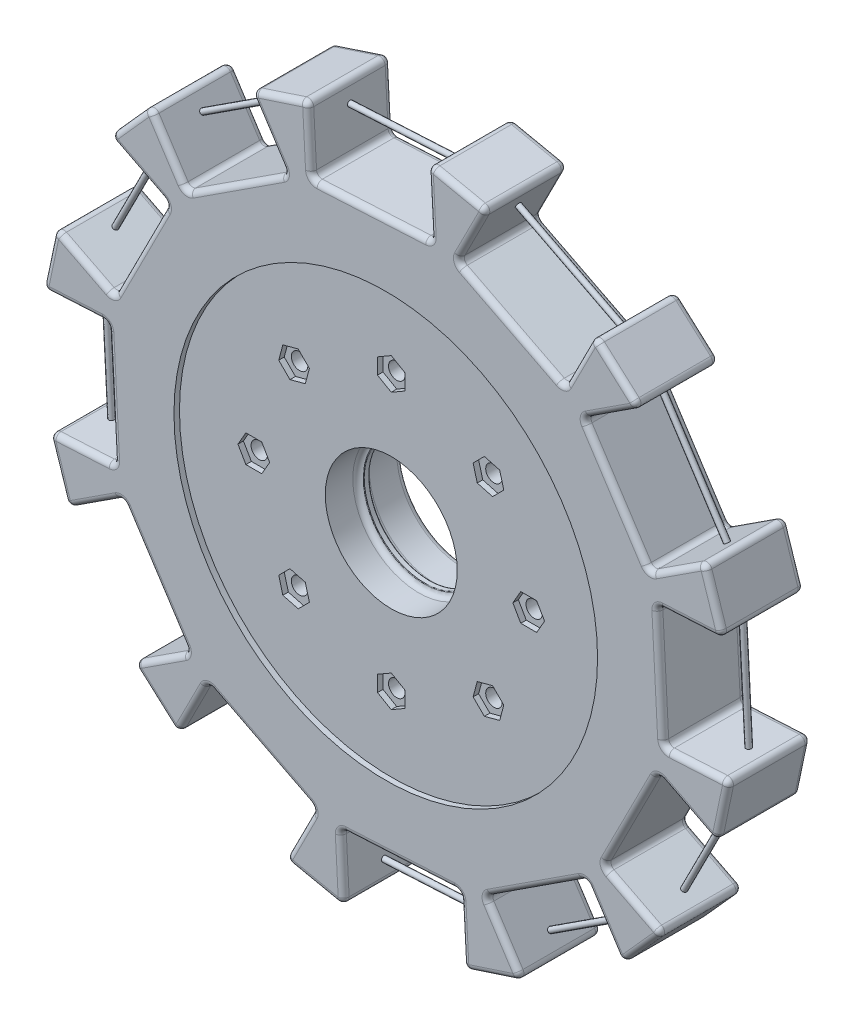
SolidWorks part; units mm, degrees
ref_plane "Front Plane" through (0, 0, 0) normal (0, 0, 1) x (1, 0, 0)
ref_plane "Top Plane" through (0, 0, 0) normal (0, 1, 0) x (1, 0, 0)
ref_plane "Right Plane" through (0, 0, 0) normal (1, 0, 0) x (0, 0, -1)
sketch "Sketch1" plane through (0, 0, 0) normal (0, 0, 1) x (1, 0, 0)
  line L0 (-18.6746, 48.6931) -> (-23.9631, 56.823)
  line L1 (40.0812, -31.4875) -> (49.0527, -13.8463)
  line L2 (50.455, -7.2284) -> (49.4041, 12.5351)
  line L3 (47.3095, 18.9676) -> (36.5176, 35.5577)
  line L4 (31.4875, 40.0812) -> (13.8463, 49.0527)
  line L5 (7.2284, 50.455) -> (-12.5351, 49.4041)
  line L6 (-18.9676, 47.3095) -> (-35.5577, 36.5176)
  line L7 (-40.0812, 31.4875) -> (-49.0527, 13.8463)
  line L8 (-50.455, 7.2284) -> (-49.4041, -12.5351)
  line L9 (-47.3095, -18.9676) -> (-36.5176, -35.5577)
  line L10 (-31.4875, -40.0812) -> (-13.8463, -49.0527)
  line L11 (-7.2284, -50.455) -> (12.5351, -49.4041)
  line L12 (18.9676, -47.3095) -> (35.5577, -36.5176)
  line L13 (-13.5868, 50.3495) -> (-14.1025, 60.0477)
  line L14 (-23.4359, 58.3186) -> (-15.4122, 60.945)
  line L15 (8.1738, 51.5067) -> (7.6588, 61.1917)
  line L16 (8.8632, 62.2234) -> (17.1251, 60.486)
  line L17 (13.4083, 50.3974) -> (17.8107, 59.0541)
  line L18 (32.8321, 40.5192) -> (37.2286, 49.1642)
  line L19 (38.7875, 49.4554) -> (45.0738, 43.8198)
  line L20 (36.8106, 36.9413) -> (44.9516, 42.237)
  line L21 (48.6931, 18.6746) -> (56.823, 23.9631)
  line L22 (58.3186, 23.4359) -> (60.945, 15.4122)
  line L23 (50.3495, 13.5868) -> (60.0477, 14.1025)
  line L24 (51.5067, -8.1738) -> (61.1917, -7.6588)
  line L25 (62.2234, -8.8632) -> (60.486, -17.1251)
  line L26 (50.3974, -13.4083) -> (59.0541, -17.8107)
  line L27 (40.5192, -32.8321) -> (49.1642, -37.2286)
  line L28 (49.4554, -38.7875) -> (43.8198, -45.0738)
  line L29 (36.9413, -36.8106) -> (42.237, -44.9516)
  line L30 (18.6746, -48.6931) -> (23.9631, -56.823)
  line L31 (23.4359, -58.3186) -> (15.4122, -60.945)
  line L32 (13.5868, -50.3495) -> (14.1025, -60.0477)
  line L33 (-8.1738, -51.5067) -> (-7.6588, -61.1917)
  line L34 (-8.8632, -62.2234) -> (-17.1251, -60.486)
  line L35 (-13.4083, -50.3974) -> (-17.8107, -59.0541)
  line L36 (-32.8321, -40.5192) -> (-37.2286, -49.1642)
  line L37 (-38.7875, -49.4554) -> (-45.0738, -43.8198)
  line L38 (-36.8106, -36.9413) -> (-44.9516, -42.237)
  line L39 (-48.6931, -18.6746) -> (-56.823, -23.9631)
  line L40 (-58.3186, -23.4359) -> (-60.945, -15.4122)
  line L41 (-50.3495, -13.5868) -> (-60.0477, -14.1025)
  line L42 (-51.5067, 8.1738) -> (-61.1917, 7.6588)
  line L43 (-62.2234, 8.8632) -> (-60.486, 17.1251)
  line L44 (-50.3974, 13.4083) -> (-59.0541, 17.8107)
  line L45 (-40.5192, 32.8321) -> (-49.1642, 37.2286)
  line L46 (-49.4554, 38.7875) -> (-43.8198, 45.0738)
  line L47 (-36.9413, 36.8106) -> (-42.237, 44.9516)
  circle A0 centre (0, 0) radius 50 construction
  arc A1 (-49.0527, 13.8463) -> (-50.3974, 13.4083) centre (-49.9441, 14.2996) cw
  arc A2 (-50.455, 7.2284) -> (-51.5067, 8.1738) centre (-51.4536, 7.1753) ccw
  arc A3 (-47.3095, -18.9676) -> (-48.6931, -18.6746) centre (-48.1478, -19.5129) ccw
  arc A4 (-49.4041, -12.5351) -> (-50.3495, -13.5868) centre (-50.4026, -12.5882) cw
  arc A5 (-36.5176, -35.5577) -> (-36.8106, -36.9413) centre (-37.3559, -36.103) cw
  arc A6 (-31.4875, -40.0812) -> (-32.8321, -40.5192) centre (-31.9408, -40.9725) ccw
  arc A7 (-13.8463, -49.0527) -> (-13.4083, -50.3974) centre (-14.2996, -49.9441) cw
  arc A8 (-7.2284, -50.455) -> (-8.1738, -51.5067) centre (-7.1753, -51.4536) ccw
  arc A9 (13.5868, -50.3495) -> (12.5351, -49.4041) centre (12.5882, -50.4026) ccw
  arc A10 (18.9676, -47.3095) -> (18.6746, -48.6931) centre (19.5129, -48.1478) ccw
  arc A11 (35.5577, -36.5176) -> (36.9413, -36.8106) centre (36.103, -37.3559) cw
  arc A12 (40.5192, -32.8321) -> (40.0812, -31.4875) centre (40.9725, -31.9408) cw
  arc A13 (49.0527, -13.8463) -> (50.3974, -13.4083) centre (49.9441, -14.2996) cw
  arc A14 (50.455, -7.2284) -> (51.5067, -8.1738) centre (51.4536, -7.1753) ccw
  arc A15 (49.4041, 12.5351) -> (50.3495, 13.5868) centre (50.4026, 12.5882) cw
  arc A16 (47.3095, 18.9676) -> (48.6931, 18.6746) centre (48.1478, 19.5129) ccw
  arc A17 (31.4875, 40.0812) -> (32.8321, 40.5192) centre (31.9408, 40.9725) ccw
  arc A18 (36.5176, 35.5577) -> (36.8106, 36.9413) centre (37.3559, 36.103) cw
  arc A19 (7.2284, 50.455) -> (8.1738, 51.5067) centre (7.1753, 51.4536) ccw
  arc A20 (13.8463, 49.0527) -> (13.4083, 50.3974) centre (14.2996, 49.9441) cw
  arc A21 (-12.5351, 49.4041) -> (-13.5868, 50.3495) centre (-12.5882, 50.4026) cw
  arc A22 (-18.9676, 47.3095) -> (-18.6746, 48.6931) centre (-19.5129, 48.1478) ccw
  arc A23 (-35.5577, 36.5176) -> (-36.9413, 36.8106) centre (-36.103, 37.3559) cw
  arc A24 (-40.0812, 31.4875) -> (-40.5192, 32.8321) centre (-40.9725, 31.9408) ccw
  arc A25 (-60.486, 17.1251) -> (-59.0541, 17.8107) centre (-59.5074, 16.9193) cw
  arc A26 (-61.1917, 7.6588) -> (-62.2234, 8.8632) centre (-61.2448, 8.6574) cw
  arc A27 (-60.945, -15.4122) -> (-60.0477, -14.1025) centre (-59.9946, -15.1011) cw
  arc A28 (-56.823, -23.9631) -> (-58.3186, -23.4359) centre (-57.3683, -23.1249) cw
  arc A29 (-45.0738, -43.8198) -> (-44.9516, -42.237) centre (-44.4063, -43.0752) cw
  arc A30 (-37.2286, -49.1642) -> (-38.7875, -49.4554) centre (-38.1199, -48.7109) cw
  arc A31 (-17.1251, -60.486) -> (-17.8107, -59.0541) centre (-16.9193, -59.5074) cw
  arc A32 (-7.6588, -61.1917) -> (-8.8632, -62.2234) centre (-8.6574, -61.2448) cw
  arc A33 (15.4122, -60.945) -> (14.1025, -60.0477) centre (15.1011, -59.9946) cw
  arc A34 (23.9631, -56.823) -> (23.4359, -58.3186) centre (23.1249, -57.3683) cw
  arc A35 (43.8198, -45.0738) -> (42.237, -44.9516) centre (43.0752, -44.4063) cw
  arc A36 (49.4554, -38.7875) -> (49.1642, -37.2286) centre (48.7109, -38.1199) ccw
  arc A37 (60.486, -17.1251) -> (59.0541, -17.8107) centre (59.5074, -16.9193) cw
  arc A38 (61.1917, -7.6588) -> (62.2234, -8.8632) centre (61.2448, -8.6574) cw
  arc A39 (56.823, 23.9631) -> (58.3186, 23.4359) centre (57.3683, 23.1249) cw
  arc A40 (60.945, 15.4122) -> (60.0477, 14.1025) centre (59.9946, 15.1011) cw
  arc A41 (37.2286, 49.1642) -> (38.7875, 49.4554) centre (38.1199, 48.7109) cw
  arc A42 (45.0738, 43.8198) -> (44.9516, 42.237) centre (44.4063, 43.0752) cw
  arc A43 (17.1251, 60.486) -> (17.8107, 59.0541) centre (16.9193, 59.5074) cw
  arc A44 (7.6588, 61.1917) -> (8.8632, 62.2234) centre (8.6574, 61.2448) cw
  arc A45 (-14.1025, 60.0477) -> (-15.4122, 60.945) centre (-15.1011, 59.9946) ccw
  arc A46 (-23.4359, 58.3186) -> (-23.9631, 56.823) centre (-23.1249, 57.3683) ccw
  arc A47 (-49.1642, 37.2286) -> (-49.4554, 38.7875) centre (-48.7109, 38.1199) cw
  arc A48 (-43.8198, 45.0738) -> (-42.237, 44.9516) centre (-43.0752, 44.4063) cw
  point P66 (0, 0)
  dimension "D1" = 100
  dimension "D7" = 1
  dimension "D2" = 1
  dimension "D6" = 12
extrude "Boss-Extrude1" add sketch "Sketch1" along normal blind 15
sketch "Sketch3" plane through (0, 0, 15) normal (0, 0, 1) x (1, 0, 0)
  circle A0 centre (0, 0) radius 12
  dimension "D1" = 24
extrude "Cut-Extrude1" cut sketch "Sketch3" against normal blind 7
sketch "Sketch4" plane through (0, 0, 0) normal (0, 0, -1) x (-1, 0, 0)
  circle A0 centre (0, 0) radius 12
  dimension "D1" = 24
extrude "Cut-Extrude2" cut sketch "Sketch4" against normal blind 7
sketch "Sketch5" plane through (0, 0, 7) normal (0, 0, -1) x (-1, 0, 0)
  circle A0 centre (0, 0) radius 11
  dimension "D1" = 22
extrude "Cut-Extrude3" cut sketch "Sketch5" against normal blind 7
fillet "Fillet1" radius 1 194 edges at (-27.2627, 41.9136, 15) (-18.5345, 47.9406, 15) (-21.3189, 52.758, 15) (-24.068, 57.7007, 15) (-19.4241, 59.6318, 15) (-14.5359, 60.8195, 15) (-13.8447, 55.1986, 15) (-13.2568, 49.659, 15) (-2.6534, 49.9295, 15) (7.9189, 50.7851, 15) (7.9163, 56.3492, 15) (8.0068, 62.0043, 15) (12.9942, 61.3547, 15) (17.8213, 59.9392, 15) (15.6095, 54.7257, 15) (13.3488, 49.6343, 15) (22.6669, 44.5669, 15) (32.2505, 40.0217, 15) (35.0304, 44.8417, 15) (37.9363, 49.6938, 15) (41.9306, 46.6376, 15) (45.4033, 42.9982, 15) (40.8811, 39.5891, 15) (36.3776, 36.3102, 15) (41.9136, 27.2627, 15) (47.9406, 18.5345, 15) (52.758, 21.3189, 15) (57.7007, 24.068, 15) (59.6318, 19.4241, 15) (60.8195, 14.5359, 15) (55.1986, 13.8447, 15) (49.659, 13.2568, 15) (49.9295, 2.6534, 15) (50.7851, -7.9189, 15) (56.3492, -7.9163, 15) (62.0043, -8.0068, 15) (61.3547, -12.9942, 15) (59.9392, -17.8213, 15) (54.7257, -15.6095, 15) (49.6343, -13.3488, 15) (44.5669, -22.6669, 15) (40.0217, -32.2505, 15) (44.8417, -35.0304, 15) (49.6938, -37.9363, 15) (46.6376, -41.9306, 15) (42.9982, -45.4033, 15) (39.5891, -40.8811, 15) (36.3102, -36.3776, 15) (27.2627, -41.9136, 15) (18.5345, -47.9406, 15) (21.3189, -52.758, 15) (24.068, -57.7007, 15) (19.4241, -59.6318, 15) (14.5359, -60.8195, 15) (13.8447, -55.1986, 15) (13.2568, -49.659, 15) (2.6534, -49.9295, 15) (-7.9189, -50.7851, 15) (-7.9163, -56.3492, 15) (-8.0068, -62.0043, 15) (-12.9942, -61.3547, 15) (-17.8213, -59.9392, 15) (-15.6095, -54.7257, 15) (-13.3488, -49.6343, 15) (-22.6669, -44.5669, 15) (-32.2505, -40.0217, 15) (-35.0304, -44.8417, 15) (-37.9363, -49.6938, 15) (-41.9306, -46.6376, 15) (-45.4033, -42.9982, 15) (-40.8811, -39.5891, 15) (-36.3776, -36.3102, 15) (-41.9136, -27.2627, 15) (-47.9406, -18.5345, 15) (-52.758, -21.3189, 15) (-57.7007, -24.068, 15) (-59.6318, -19.4241, 15) (-60.8195, -14.5359, 15) (-55.1986, -13.8447, 15) (-49.659, -13.2568, 15) (-49.9295, -2.6534, 15) (-50.7851, 7.9189, 15) (-56.3492, 7.9163, 15) (-62.0043, 8.0068, 15) (-61.3547, 12.9942, 15) (-59.9392, 17.8213, 15) (-54.7257, 15.6095, 15) (-49.6343, 13.3488, 15) (-44.5669, 22.6669, 15) (-40.0217, 32.2505, 15) (-44.8417, 35.0304, 15) (-49.6938, 37.9363, 15) (-46.6376, 41.9306, 15) (-42.9982, 45.4033, 15) (-39.5891, 40.8811, 15) (-36.3102, 36.3776, 15) (12, 0, 15) (-39.5891, 40.8811, 0) (-42.9982, 45.4033, 0) (-46.6376, 41.9306, 0) (-49.6938, 37.9363, 0) (-44.8417, 35.0304, 0) (-40.0217, 32.2505, 0) (-44.5669, 22.6669, 0) (-49.6343, 13.3488, 0) (-54.7257, 15.6095, 0) (-59.9392, 17.8213, 0) (-61.3547, 12.9942, 0) (-62.0043, 8.0068, 0) (-56.3492, 7.9163, 0) (-50.7851, 7.9189, 0) (-49.9295, -2.6534, 0) (-49.659, -13.2568, 0) (-55.1986, -13.8447, 0) (-60.8195, -14.5359, 0) (-59.6318, -19.4241, 0) (-57.7007, -24.068, 0) (-52.758, -21.3189, 0) (-47.9406, -18.5345, 0) (-41.9136, -27.2627, 0) (-36.3776, -36.3102, 0) (-40.8811, -39.5891, 0) (-45.4033, -42.9982, 0) (-41.9306, -46.6376, 0) (-37.9363, -49.6938, 0) (-35.0304, -44.8417, 0) (-32.2505, -40.0217, 0) (-22.6669, -44.5669, 0) (-13.3488, -49.6343, 0) (-15.6095, -54.7257, 0) (-17.8213, -59.9392, 0) (-12.9942, -61.3547, 0) (-8.0068, -62.0043, 0) (-7.9163, -56.3492, 0) (-7.9189, -50.7851, 0) (2.6534, -49.9295, 0) (13.2568, -49.659, 0) (13.8447, -55.1986, 0) (14.5359, -60.8195, 0) (19.4241, -59.6318, 0) (24.068, -57.7007, 0) (21.3189, -52.758, 0) (18.5345, -47.9406, 0) (27.2627, -41.9136, 0) (36.3102, -36.3776, 0) (39.5891, -40.8811, 0) (42.9982, -45.4033, 0) (46.6376, -41.9306, 0) (49.6938, -37.9363, 0) (44.8417, -35.0304, 0) (40.0217, -32.2505, 0) (44.5669, -22.6669, 0) (49.6343, -13.3488, 0) (54.7257, -15.6095, 0) (59.9392, -17.8213, 0) (61.3547, -12.9942, 0) (62.0043, -8.0068, 0) (56.3492, -7.9163, 0) (50.7851, -7.9189, 0) (49.9295, 2.6534, 0) (49.659, 13.2568, 0) (55.1986, 13.8447, 0) (60.8195, 14.5359, 0) (59.6318, 19.4241, 0) (57.7007, 24.068, 0) (52.758, 21.3189, 0) (47.9406, 18.5345, 0) (41.9136, 27.2627, 0) (36.3776, 36.3102, 0) (40.8811, 39.5891, 0) (45.4033, 42.9982, 0) (41.9306, 46.6376, 0) (37.9363, 49.6938, 0) (35.0304, 44.8417, 0) (32.2505, 40.0217, 0) (22.6669, 44.5669, 0) (13.3488, 49.6343, 0) (15.6095, 54.7257, 0) (17.8213, 59.9392, 0) (12.9942, 61.3547, 0) (8.0068, 62.0043, 0) (7.9163, 56.3492, 0) (7.9189, 50.7851, 0) (-2.6534, 49.9295, 0) (-13.2568, 49.659, 0) (-13.8447, 55.1986, 0) (-14.5359, 60.8195, 0) (-19.4241, 59.6318, 0) (-24.068, 57.7007, 0) (-21.3189, 52.758, 0) (-18.5345, 47.9406, 0) (-27.2627, 41.9136, 0) (-36.3102, 36.3776, 0) (-12, 0, 0)
fillet "Fillet2" radius 1 2 edges at (12, 0, 8) (-12, 0, 7)
fillet "Fillet3" radius 0.1 2 edges at (-11, 0, 7) (11, 0, 8)
sketch "Sketch6" plane through (0, 0, 0) normal (0, 0, -1) x (-1, 0, 0)
  circle A0 centre (0, 25) radius 1.5
  circle A1 centre (17.6777, 17.6777) radius 1.5
  circle A2 centre (25, 0) radius 1.5
  circle A3 centre (17.6777, -17.6777) radius 1.5
  circle A4 centre (0, -25) radius 1.5
  circle A5 centre (-17.6777, -17.6777) radius 1.5
  circle A6 centre (-25, 0) radius 1.5
  circle A7 centre (-17.6777, 17.6777) radius 1.5
  point P20 (0, 0)
  dimension "D2" = 3
  dimension "D1" = 25
  dimension "D3" = 8
extrude "Cut-Extrude4" cut sketch "Sketch6" against normal blind 37
sketch "Sketch7" plane through (0, 0, 0) normal (0, 0, -1) x (-1, 0, 0)
  line L0 (15.6364, 15.6364) -> (18.4248, 14.8893)
  line L1 (0, 22.1132) -> (2.5, 23.5566)
  line L2 (2.5, 23.5566) -> (2.5, 26.4434)
  line L3 (2.5, 26.4434) -> (0, 27.8868)
  line L4 (0, 27.8868) -> (-2.5, 26.4434)
  line L5 (-2.5, 26.4434) -> (-2.5, 23.5566)
  line L6 (-2.5, 23.5566) -> (0, 22.1132)
  line L7 (18.4248, 14.8893) -> (20.4661, 16.9305)
  line L8 (20.4661, 16.9305) -> (19.7189, 19.7189)
  line L9 (19.7189, 19.7189) -> (16.9305, 20.4661)
  line L10 (16.9305, 20.4661) -> (14.8893, 18.4248)
  line L11 (14.8893, 18.4248) -> (15.6364, 15.6364)
  line L12 (22.1132, 0) -> (23.5566, -2.5)
  line L13 (23.5566, -2.5) -> (26.4434, -2.5)
  line L14 (26.4434, -2.5) -> (27.8868, 0)
  line L15 (27.8868, 0) -> (26.4434, 2.5)
  line L16 (26.4434, 2.5) -> (23.5566, 2.5)
  line L17 (23.5566, 2.5) -> (22.1132, 0)
  line L18 (15.6364, -15.6364) -> (14.8893, -18.4248)
  line L19 (14.8893, -18.4248) -> (16.9305, -20.4661)
  line L20 (16.9305, -20.4661) -> (19.7189, -19.7189)
  line L21 (19.7189, -19.7189) -> (20.4661, -16.9305)
  line L22 (20.4661, -16.9305) -> (18.4248, -14.8893)
  line L23 (18.4248, -14.8893) -> (15.6364, -15.6364)
  line L24 (0, -22.1132) -> (-2.5, -23.5566)
  line L25 (-2.5, -23.5566) -> (-2.5, -26.4434)
  line L26 (-2.5, -26.4434) -> (0, -27.8868)
  line L27 (0, -27.8868) -> (2.5, -26.4434)
  line L28 (2.5, -26.4434) -> (2.5, -23.5566)
  line L29 (2.5, -23.5566) -> (0, -22.1132)
  line L30 (-15.6364, -15.6364) -> (-18.4248, -14.8893)
  line L31 (-18.4248, -14.8893) -> (-20.4661, -16.9305)
  line L32 (-20.4661, -16.9305) -> (-19.7189, -19.7189)
  line L33 (-19.7189, -19.7189) -> (-16.9305, -20.4661)
  line L34 (-16.9305, -20.4661) -> (-14.8893, -18.4248)
  line L35 (-14.8893, -18.4248) -> (-15.6364, -15.6364)
  line L36 (-22.1132, 0) -> (-23.5566, 2.5)
  line L37 (-23.5566, 2.5) -> (-26.4434, 2.5)
  line L38 (-26.4434, 2.5) -> (-27.8868, 0)
  line L39 (-27.8868, 0) -> (-26.4434, -2.5)
  line L40 (-26.4434, -2.5) -> (-23.5566, -2.5)
  line L41 (-23.5566, -2.5) -> (-22.1132, 0)
  line L42 (-15.6364, 15.6364) -> (-14.8893, 18.4248)
  line L43 (-14.8893, 18.4248) -> (-16.9305, 20.4661)
  line L44 (-16.9305, 20.4661) -> (-19.7189, 19.7189)
  line L45 (-19.7189, 19.7189) -> (-20.4661, 16.9305)
  line L46 (-20.4661, 16.9305) -> (-18.4248, 14.8893)
  line L47 (-18.4248, 14.8893) -> (-15.6364, 15.6364)
  circle A0 centre (0, 25) radius 2.5 construction
  point P54 (0, 0)
  dimension "D1" = 5
  dimension "D2" = 8
extrude "Cut-Extrude5" cut sketch "Sketch7" against normal blind 2
sketch "Sketch8" plane through (0, 0, 15) normal (0, 0, 1) x (1, 0, 0)
  line L0 (15.6364, 15.6364) -> (18.4248, 14.8893)
  line L1 (0, 22.1132) -> (2.5, 23.5566)
  line L2 (2.5, 23.5566) -> (2.5, 26.4434)
  line L3 (2.5, 26.4434) -> (0, 27.8868)
  line L4 (0, 27.8868) -> (-2.5, 26.4434)
  line L5 (-2.5, 26.4434) -> (-2.5, 23.5566)
  line L6 (-2.5, 23.5566) -> (0, 22.1132)
  line L7 (18.4248, 14.8893) -> (20.4661, 16.9305)
  line L8 (20.4661, 16.9305) -> (19.7189, 19.7189)
  line L9 (19.7189, 19.7189) -> (16.9305, 20.4661)
  line L10 (16.9305, 20.4661) -> (14.8893, 18.4248)
  line L11 (14.8893, 18.4248) -> (15.6364, 15.6364)
  line L12 (22.1132, 0) -> (23.5566, -2.5)
  line L13 (23.5566, -2.5) -> (26.4434, -2.5)
  line L14 (26.4434, -2.5) -> (27.8868, 0)
  line L15 (27.8868, 0) -> (26.4434, 2.5)
  line L16 (26.4434, 2.5) -> (23.5566, 2.5)
  line L17 (23.5566, 2.5) -> (22.1132, 0)
  line L18 (15.6364, -15.6364) -> (14.8893, -18.4248)
  line L19 (14.8893, -18.4248) -> (16.9305, -20.4661)
  line L20 (16.9305, -20.4661) -> (19.7189, -19.7189)
  line L21 (19.7189, -19.7189) -> (20.4661, -16.9305)
  line L22 (20.4661, -16.9305) -> (18.4248, -14.8893)
  line L23 (18.4248, -14.8893) -> (15.6364, -15.6364)
  line L24 (0, -22.1132) -> (-2.5, -23.5566)
  line L25 (-2.5, -23.5566) -> (-2.5, -26.4434)
  line L26 (-2.5, -26.4434) -> (0, -27.8868)
  line L27 (0, -27.8868) -> (2.5, -26.4434)
  line L28 (2.5, -26.4434) -> (2.5, -23.5566)
  line L29 (2.5, -23.5566) -> (0, -22.1132)
  line L30 (-15.6364, -15.6364) -> (-18.4248, -14.8893)
  line L31 (-18.4248, -14.8893) -> (-20.4661, -16.9305)
  line L32 (-20.4661, -16.9305) -> (-19.7189, -19.7189)
  line L33 (-19.7189, -19.7189) -> (-16.9305, -20.4661)
  line L34 (-16.9305, -20.4661) -> (-14.8893, -18.4248)
  line L35 (-14.8893, -18.4248) -> (-15.6364, -15.6364)
  line L36 (-22.1132, 0) -> (-23.5566, 2.5)
  line L37 (-23.5566, 2.5) -> (-26.4434, 2.5)
  line L38 (-26.4434, 2.5) -> (-27.8868, 0)
  line L39 (-27.8868, 0) -> (-26.4434, -2.5)
  line L40 (-26.4434, -2.5) -> (-23.5566, -2.5)
  line L41 (-23.5566, -2.5) -> (-22.1132, 0)
  line L42 (-15.6364, 15.6364) -> (-14.8893, 18.4248)
  line L43 (-14.8893, 18.4248) -> (-16.9305, 20.4661)
  line L44 (-16.9305, 20.4661) -> (-19.7189, 19.7189)
  line L45 (-19.7189, 19.7189) -> (-20.4661, 16.9305)
  line L46 (-20.4661, 16.9305) -> (-18.4248, 14.8893)
  line L47 (-18.4248, 14.8893) -> (-15.6364, 15.6364)
  circle A0 centre (0, 25) radius 2.5 construction
  point P53 (0, 0)
  dimension "D1" = 5
  dimension "D2" = 8
extrude "Cut-Extrude6" cut sketch "Sketch8" against normal blind 2
sketch "Sketch9" plane through (-5.9403, 9.1319, 0) normal (0.5453, -0.8383, 0) x (0.8383, 0.5453, 0)
  line L0 (58.025, 14) -> (58.025, 1) construction
  circle A0 centre (58.025, 7.5) radius 0.5
  dimension "D1" = 1
extrude "Boss-Extrude2" add sketch "Sketch9" along normal blind 23
sketch "Sketch10" plane through (-0.5785, 10.8786, 0) normal (0.0531, -0.9986, 0) x (0.9986, 0.0531, 0)
  line L0 (58.025, 14) -> (58.025, 1) construction
  circle A0 centre (58.025, 7.5) radius 0.5
  dimension "D1" = 1
extrude "Boss-Extrude3" add sketch "Sketch10" along normal blind 23
sketch "Sketch11" plane through (4.9383, 9.7104, 0) normal (-0.4533, -0.8914, 0) x (0.8914, -0.4533, 0)
  line L0 (58.025, 14) -> (58.025, 1) construction
  circle A0 centre (58.025, 7.5) radius 0.5
  dimension "D1" = 1
extrude "Boss-Extrude4" add sketch "Sketch11" along normal blind 23
sketch "Sketch12" plane through (9.1319, 5.9403, 0) normal (-0.8383, -0.5453, 0) x (0, 0, 1)
  line L0 (14, -58.025) -> (1, -58.025) construction
  circle A0 centre (7.5, -58.025) radius 0.5
  dimension "D1" = 1
extrude "Boss-Extrude5" add sketch "Sketch12" along normal blind 23
sketch "Sketch13" plane through (10.8786, 0.5785, 0) normal (-0.9986, -0.0531, 0) x (0, 0, 1)
  line L0 (14, -58.025) -> (1, -58.025) construction
  circle A0 centre (7.5, -58.025) radius 0.5
  dimension "D1" = 1
extrude "Boss-Extrude6" add sketch "Sketch13" along normal blind 23
sketch "Sketch14" plane through (9.7104, -4.9383, 0) normal (-0.8914, 0.4533, 0) x (0, 0, 1)
  line L0 (14, -58.025) -> (1, -58.025) construction
  circle A0 centre (7.5, -58.025) radius 0.5
  dimension "D1" = 1
extrude "Boss-Extrude7" add sketch "Sketch14" along normal blind 23
sketch "Sketch15" plane through (5.9403, -9.1319, 0) normal (-0.5453, 0.8383, 0) x (0.8383, 0.5453, 0)
  line L0 (-58.025, -14) -> (-58.025, -1) construction
  circle A0 centre (-58.025, -7.5) radius 0.5
  dimension "D1" = 1
extrude "Boss-Extrude8" add sketch "Sketch15" along normal blind 23
sketch "Sketch16" plane through (0.5785, -10.8786, 0) normal (-0.0531, 0.9986, 0) x (0.9986, 0.0531, 0)
  line L0 (-58.025, -14) -> (-58.025, -1) construction
  circle A0 centre (-58.025, -7.5) radius 0.5
  dimension "D1" = 1
extrude "Boss-Extrude9" add sketch "Sketch16" along normal blind 23
sketch "Sketch17" plane through (-4.9383, -9.7104, 0) normal (0.4533, 0.8914, 0) x (0.8914, -0.4533, 0)
  line L0 (-58.025, -14) -> (-58.025, -1) construction
  circle A0 centre (-58.025, -7.5) radius 0.5
  dimension "D1" = 1
extrude "Boss-Extrude10" add sketch "Sketch17" along normal blind 23
sketch "Sketch18" plane through (-9.1319, -5.9403, 0) normal (0.8383, 0.5453, 0) x (0, 0, -1)
  line L0 (-14, 58.025) -> (-1, 58.025) construction
  circle A0 centre (-7.5, 58.025) radius 0.5
  dimension "D1" = 1
extrude "Boss-Extrude11" add sketch "Sketch18" along normal blind 23
sketch "Sketch19" plane through (-10.8786, -0.5785, 0) normal (0.9986, 0.0531, 0) x (0, 0, -1)
  line L0 (-14, 58.025) -> (-1, 58.025) construction
  circle A0 centre (-7.5, 58.025) radius 0.5
  dimension "D1" = 1
extrude "Boss-Extrude12" add sketch "Sketch19" along normal blind 23
sketch "Sketch20" plane through (-9.7104, 4.9383, 0) normal (0.8914, -0.4533, 0) x (0, 0, -1)
  line L0 (-14, 58.025) -> (-1, 58.025) construction
  circle A0 centre (-7.5, 58.025) radius 0.5
  dimension "D1" = 1
extrude "Boss-Extrude13" add sketch "Sketch20" along normal blind 23
sketch "Sketch23" plane through (0, 0, 15) normal (0, 0, 1) x (1, 0, 0)
  circle A0 centre (0, 0) radius 38.5239
extrude "Cut-Extrude8" cut sketch "Sketch23" against normal blind 1
sketch "Sketch24" plane through (0, 0, 0) normal (0, 0, -1) x (-1, 0, 0)
  line L1 (12.482, 48.4055) -> (-7.2815, 49.4564) construction
  line L2 (2.6003, 48.931) -> (0, 0) construction
  circle A1 centre (2.1227, 39.9436) radius 1
  dimension "D1" = 40
  dimension "D2" = 2
extrude "Boss-Extrude14" add sketch "Sketch24" along normal blind 1
fillet "Fillet4" radius 0.5 1 edges at (-3.1227, 39.9436, -1)
sketch "Sketch25" plane through (0, 0, 0) normal (0, 0, -1) x (-1, 0, 0)
  line L0 (-12.7884, 60.3761) -> (0, 0) construction
  line L1 (-8.6574, 61.2448) -> (-16.9193, 59.5074) construction
  circle A0 centre (-8.2886, 39.1318) radius 1
  dimension "D2" = 2
  dimension "D1" = 40
extrude "Cut-Extrude9" cut sketch "Sketch25" against normal blind 1
fillet "Fillet5" radius 0.5 1 edges at (7.2886, 39.1318, 1)
